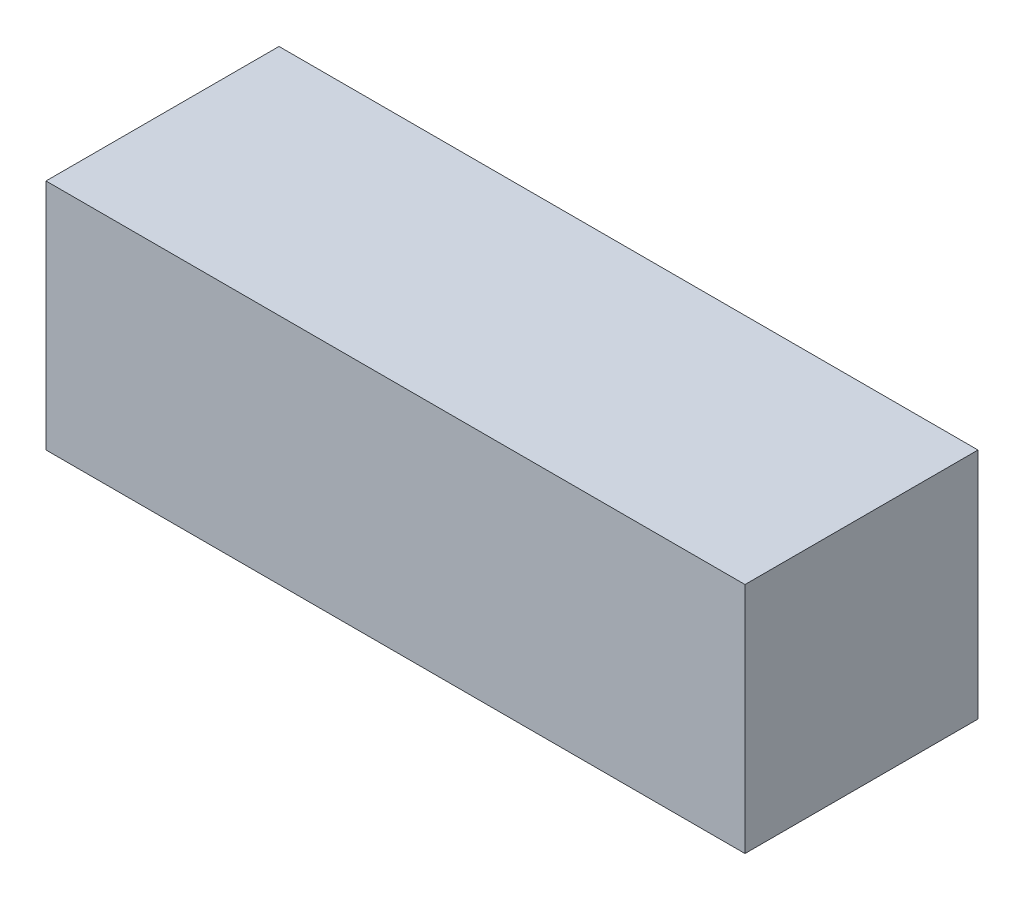
SolidWorks part; units mm, degrees
ref_plane "Front Plane" through (0, 0, 0) normal (0, 0, 1) x (1, 0, 0)
ref_plane "Top Plane" through (0, 0, 0) normal (0, 1, 0) x (1, 0, 0)
ref_plane "Right Plane" through (0, 0, 0) normal (1, 0, 0) x (0, 0, -1)
sketch "Sketch1" plane through (0, 0, 0) normal (1, 0, 0) x (0, 0, -1)
  line L1 (-2, -2) -> (2, -2)
  line L2 (-2, -2) -> (-2, 2)
  line L3 (-2, 2) -> (2, 2)
  line L4 (2, -2) -> (2, 2)
  line L5 (-2, -2) -> (2, 2) construction
  line L6 (-2, 2) -> (2, -2) construction
  point P0 (0, 0)
  dimension "D1" = 4
  dimension "D2" = 4
extrude "Boss-Extrude1" add sketch "Sketch1" along normal mid plane 12
sketch "Sketch2" [suppressed] plane through (0, 2, 0) normal (0, 1, 0) x (1, 0, 0)
  line L0 (6, -2) -> (-6, -2) construction
  line L1 (6, 2) -> (2, 2)
  line L2 (6, 2) -> (6, -2)
  line L3 (6, -2) -> (2, -2)
  line L4 (2, 2) -> (2, -2)
  dimension "D1" = 4
extrude "Cut-Extrude1" [suppressed] cut sketch "Sketch2" against normal through all
equation "\"shaft-diameter\" =20mm"
equation "\"key-length\"=12mm"
equation "\"key-width\"=4mm"
equation "\"D1@Boss-Extrude1\"=\"key-length\""
equation "\"D2@Sketch1\"=\"key-width\""
